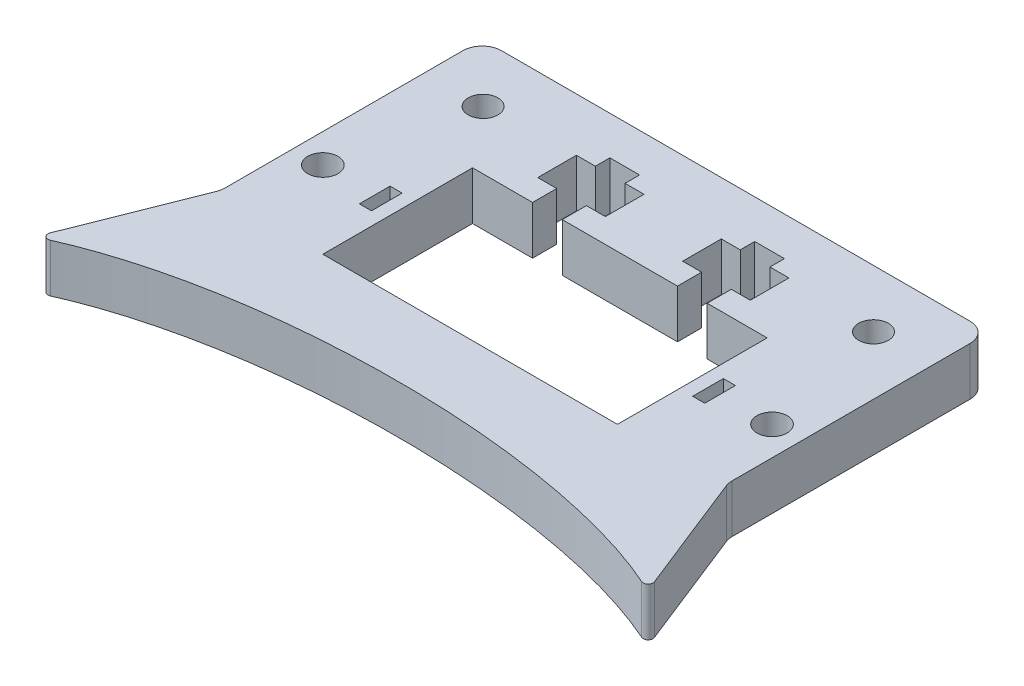
SolidWorks part; units mm, degrees
ref_plane "Front Plane" through (0, 0, 0) normal (0, 0, 1) x (1, 0, 0)
ref_plane "Top Plane" through (0, 0, 0) normal (0, 1, 0) x (1, 0, 0)
ref_plane "Right Plane" through (0, 0, 0) normal (1, 0, 0) x (0, 0, -1)
sketch "Sketch1" plane through (0, 0, 0) normal (0, 1, 0) x (1, 0, 0)
  line L1 (-52.5, -35) -> (52.5, -35)
  line L2 (-52.5, -35) -> (-52.5, 35)
  line L3 (-52.5, 35) -> (52.5, 35)
  line L4 (52.5, -35) -> (52.5, 35)
  line L5 (0, 35) -> (0, -35) construction
  line L6 (-52.5, 0) -> (52.5, 0) construction
  point P0 (0, 0)
  dimension "D1" = 105
  dimension "D2" = 70
extrude "Boss-Extrude1" add sketch "Sketch1" along normal blind 10
sketch "Sketch2" plane through (0, 10, 0) normal (0, 1, 0) x (1, 0, 0)
  line L6 (-30.5, 11) -> (30.5, 11)
  line L7 (-30.5, 11) -> (-30.5, -20)
  line L8 (-30.5, -20) -> (30.5, -20)
  line L9 (30.5, 11) -> (30.5, -20)
  line L10 (0, -20) -> (0, 11) construction
  line L11 (-30.5, -4.5) -> (30.5, -4.5) construction
  line L12 (0, 0) -> (0, -20) construction
  line L14 (-52.5, -35) -> (52.5, -35) construction
  point P0 (0, -4.5)
  dimension "D1" = 31
  dimension "D2" = 61
  dimension "D3" = 15
extrude "Cut-Extrude1" cut sketch "Sketch2" against normal through all
sketch "Sketch3" plane through (0, 10, 0) normal (0, 1, 0) x (1, 0, 0)
  line L0 (-15, 35) -> (-15, 11.6634) construction
  line L1 (52.5, 35) -> (-52.5, 35) construction
  line L3 (-22, 24) -> (-22, 16)
  line L4 (-18.075, 7.3268) -> (-11.925, 7.3268)
  line L5 (-18.075, 7.3268) -> (-18.075, 16)
  line L6 (-18.075, 16) -> (-11.925, 16)
  line L7 (-11.925, 7.3268) -> (-11.925, 16)
  line L8 (-15, 16) -> (-15, 7.3268) construction
  line L9 (-18.075, 11.6634) -> (-11.925, 11.6634) construction
  line L10 (-22, 24) -> (-8, 24)
  line L11 (-22, 16) -> (-8, 16)
  line L12 (-8, 24) -> (-8, 16)
  line L13 (-15, 16) -> (-15, 24) construction
  line L14 (-22, 20) -> (-8, 20) construction
  line L15 (0, 0) -> (0, 35) construction
  line L16 (-11.925, 21) -> (-18.075, 21)
  line L17 (-11.925, 21) -> (-11.925, 27)
  line L18 (-11.925, 27) -> (-18.075, 27)
  line L19 (-18.075, 21) -> (-18.075, 27)
  line L20 (-15, 27) -> (-15, 21) construction
  line L21 (-11.925, 24) -> (-18.075, 24) construction
  line L22 (30.5, 11) -> (-30.5, 11) construction
  point P10 (-15, 20)
  dimension "D1" = 6.15
  dimension "D2" = 5
  dimension "D3" = 14
  dimension "D4" = 8
  dimension "D5" = 16
  dimension "D6" = 15
extrude "Cut-Extrude2" cut sketch "Sketch3" against normal blind 10 contours L7 L6 L5 | L16 L19 L10 L3 L11 L6 L12 L17 | L19 L16 L17 L10 | L19 L10 L17 L18 region at (-15, 10, -19.5069) region at (-15, 10, -25.5) region at (-15, 10, -22.5) region at (-15, 10, -11.6634)
sketch "Sketch4" plane through (0, 10, 0) normal (0, 1, 0) x (1, 0, 0)
  line L2 (-46.5, -4) -> (-34.5, -4) construction
  line L3 (-18.075, 11) -> (-30.5, 11) construction
  line L4 (-33.25, -0.825) -> (-35.75, -0.825)
  line L5 (-33.25, -0.825) -> (-33.25, -7.175)
  line L6 (-33.25, -7.175) -> (-35.75, -7.175)
  line L7 (-35.75, -0.825) -> (-35.75, -7.175)
  line L8 (-34.5, -7.175) -> (-34.5, -0.825) construction
  line L9 (-33.25, -4) -> (-35.75, -4) construction
  line L10 (-30.5, 11) -> (-30.5, -20) construction
  circle A0 centre (-46.5, -4) radius 3.125
  dimension "D1" = 6.25
  dimension "D2" = 15
  dimension "D3" = 16
  dimension "D4" = 2.5
  dimension "D5" = 6.35
  dimension "D6" = 2.75
extrude "Cut-Extrude3" cut sketch "Sketch4" against normal through all
sketch "Sketch5" plane through (0, 0, 0) normal (0, 1, 0) x (1, 0, 0)
  line L0 (0, 0) -> (0, -65) construction
  line L1 (-52.5, -35) -> (52.5, -35) construction
  line L2 (-52.5, -19.0391) -> (-63.479, -46.7424)
  line L3 (-52.5, 35) -> (-52.5, -35) construction
  line L4 (-52.5, -19.0391) -> (0, -35)
  ellipse E0 centre (0, -65) end of major axis (-80, -65) minor radius 30
  dimension "D1" = 160
  dimension "D2" = 65
extrude "Boss-Extrude2" add sketch "Sketch5" along normal up to surface (10 mm away) contours E0 L4 L2 region at (-39.8663, 0, 32.2303) up to face at (-46.5, 10, 7.125)
sketch "Sketch6" plane through (0, 10, 0) normal (0, 1, 0) x (1, 0, 0)
  circle A0 centre (-40.4209, 23.095) radius 3.075
  dimension "D1" = 6.15
extrude "Cut-Extrude4" cut sketch "Sketch6" against normal through all
mirror "Mirror1" about plane through (0, 0, 0) normal (1, 0, 0) of "Cut-Extrude4", "Cut-Extrude3", "Cut-Extrude2", "Boss-Extrude2"
fillet "Fillet2" radius 1 2 edges at (-63.479, 5, 46.7424) (63.479, 5, 46.7424)
fillet "Fillet1" radius 4 4 edges at (-52.5, 5, 19.0391) (-52.5, 5, -35) (52.5, 5, 19.0391) (52.5, 5, -35)
